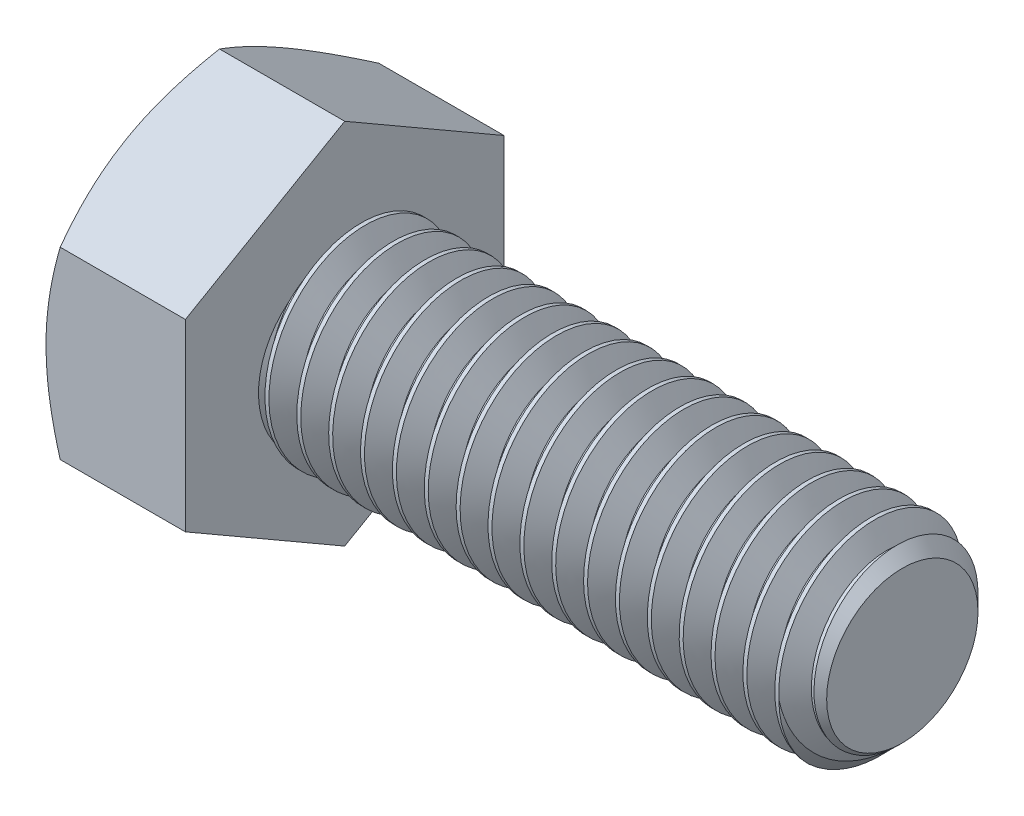
SolidWorks part; units mm, degrees
ref_plane "Front Plane" through (0, 0, 0) normal (0, 0, 1) x (1, 0, 0)
ref_plane "Top Plane" through (0, 0, 0) normal (0, 1, 0) x (1, 0, 0)
ref_plane "Right Plane" through (0, 0, 0) normal (1, 0, 0) x (0, 0, -1)
sketch "Sketch1" plane through (0, 0, 0) normal (0, 0, 1) x (1, 0, 0)
  line L0 (-8.75, 0) -> (8.75, 0) construction
  line L1 (-5.25, 4) -> (-5.25, -4) construction
  line L2 (-8.75, 4) -> (-8.75, -4) construction
  line L3 (8.75, 2.5) -> (8.75, -2.5) construction
  point P8 (5.95, -2.5)
  dimension "D1" = 2.8
  dimension "Thread Dia" = 5
  dimension "Hex" = 8
  dimension "Head Ht" = 3.5
  dimension "Length" = 14
ref_plane "Plane2" through (8.75, 0, 0) normal (1, 0, 0) x (0, 0, -1)
sketch "Sketch2" plane through (8.75, 0, 0) normal (1, 0, 0) x (0, 0, -1)
  circle A0 centre (0, 0) radius 2.5
extrude "Boss-Extrude1" add sketch "Sketch2" against normal up to vertex (14 mm away) up to point (-5.25, -4, 0)
sketch "Sketch4" plane through (8.75, 0, 0) normal (1, 0, 0) x (0, 0, -1)
  circle A1 centre (0, 0) radius 2.5
  circle A2 centre (0, 0) radius 2.5
  dimension "D1" = 0
curve "Helix/Spiral1" pitch 0.8 height 14.8 turns 18.5 parameters "Pitch"=0.8
chamfer "Chamfer1" distance 0.6 angle 45 1 edges at (8.75, 0, -2.5)
sketch "Sketch5" plane through (0, 0, 0) normal (0, 0, 1) x (1, 0, 0)
  line L0 (8.75, 2.5) -> (9.05, 1.9804)
  line L1 (9.05, 1.9804) -> (9.15, 1.9804)
  line L2 (9.15, 1.9804) -> (9.45, 2.5)
  line L3 (8.75, 2.5) -> (9.45, 2.5)
  line L4 (9.1, 1.9804) -> (9.1, 2.5) construction
  line L5 (8.9, 2.2402) -> (9.3, 2.2402) construction
  line L6 (8.75, -2.5) -> (8.75, 2.5) construction
  dimension "D1" = 60
  dimension "D2" = 0.1
  dimension "D3" = 0.4
sweep "Cut-Sweep1" cut profiles "Sketch5" path "Helix/Spiral1" align with end faces yes
sketch "Sketch3" plane through (-5.25, 0, 0) normal (-1, 0, 0) x (0, 0, 1)
  line L0 (0, 4) -> (0, -4) construction
  line L1 (-4, -2.3094) -> (0, -4.6188)
  line L2 (0, -4.6188) -> (4, -2.3094)
  line L3 (4, -2.3094) -> (4, 2.3094)
  line L4 (4, 2.3094) -> (0, 4.6188)
  line L5 (0, 4.6188) -> (-4, 2.3094)
  line L6 (-4, 2.3094) -> (-4, -2.3094)
  circle A0 centre (0, 0) radius 4 construction
extrude "Boss-Extrude2" add sketch "Sketch3" along normal up to vertex (3.5 mm away) up to point (-8.75, -4, 0)
sketch "Sketch6" plane through (-8.75, 0, 0) normal (-1, 0, 0) x (0, 0, 1)
  circle A0 centre (0, 0) radius 4 construction
  circle A1 centre (0, 0) radius 4
extrude "Cut-Extrude1" cut sketch "Sketch6" against normal through all draft 60 flip side to cut
sketch "Sketch9" plane through (0, 0, 0) normal (0, 0, 1) x (1, 0, 0)
  line L0 (-5.25, 2.5) -> (-5.25, 0)
  line L1 (-5.25, 0) -> (-42.75, 0)
  line L2 (-42.75, 0) -> (-45.25, 2.5)
  line L3 (-45.25, 2.5) -> (-5.25, 2.5)
  line L4 (-8.75, 0) -> (8.75, 0) construction
  line L5 (-5.25, 4) -> (-5.25, -4) construction
  line L6 (8.75, 2.5) -> (8.75, -2.5) construction
  dimension "D1" = 45
  dimension "MinThreadLg" = 54
revolve "Revolve1" [suppressed] add sketch "Sketch9" angle 360 about L1
equation "\"D2@Sketch5\" = \"Pitch@Helix/Spiral1\"*.125"
equation "\"D3@Sketch5\" = \"Pitch@Helix/Spiral1\"*.50"
equation "\"D3@Helix/Spiral1\" = \"Length@Sketch1\"+\"Pitch@Helix/Spiral1\""
equation "\"D1@Chamfer1\" = \"Pitch@Helix/Spiral1\"*.750"
equation "\"D1@Sketch1\" = \"Pitch@Helix/Spiral1\"*3.50"
